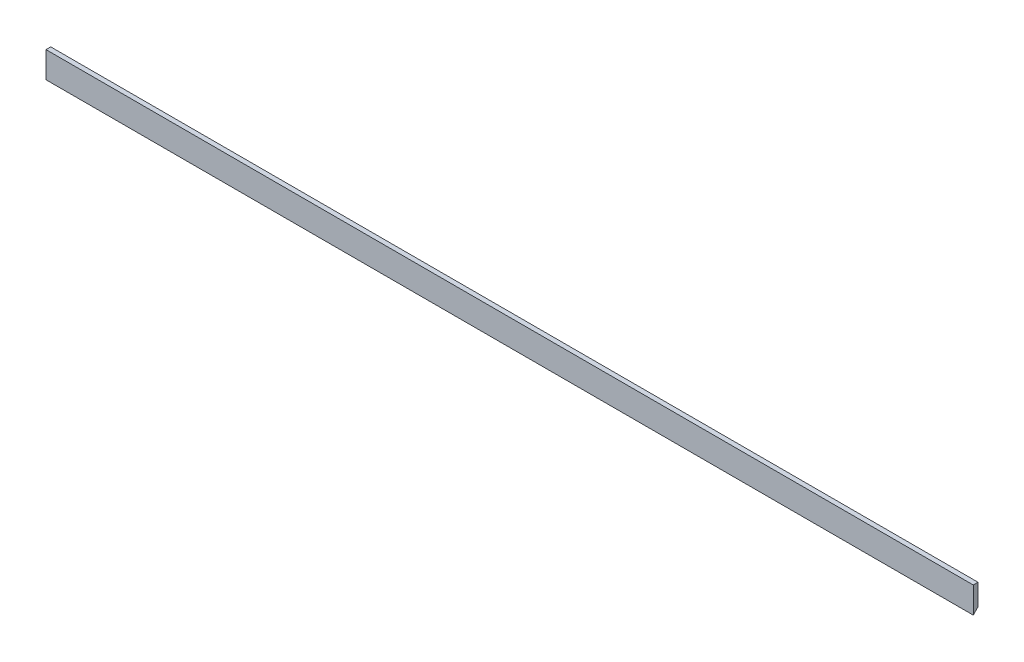
SolidWorks part; units mm, degrees
material "Balsa"
ref_plane "Front Plane" through (0, 0, 0) normal (0, 0, 1) x (1, 0, 0)
ref_plane "Top Plane" through (0, 0, 0) normal (0, 1, 0) x (1, 0, 0)
ref_plane "Right Plane" through (0, 0, 0) normal (1, 0, 0) x (0, 0, -1)
sketch "Sketch1" plane through (0, 0, 0) normal (1, 0, 0) x (0, 0, -1)
  line L1 (-1.5875, 8.75) -> (1.5875, 8.75)
  line L2 (-1.5875, 8.75) -> (-1.5875, -8.75)
  line L3 (-1.5875, -8.75) -> (1.5875, -8.75)
  line L4 (1.5875, 8.75) -> (1.5875, -8.75)
  line L5 (-1.5875, 8.75) -> (1.5875, -8.75) construction
  line L6 (-1.5875, -8.75) -> (1.5875, 8.75) construction
  point P0 (0, 0)
  dimension "D1" = 3.175
  dimension "D2" = 17.5
extrude "Boss-Extrude1" add sketch "Sketch1" along normal mid plane 621
chamfer "Chamfer1" distance 3.175 angle 45 1 edges at (0, -8.75, -1.5875)
